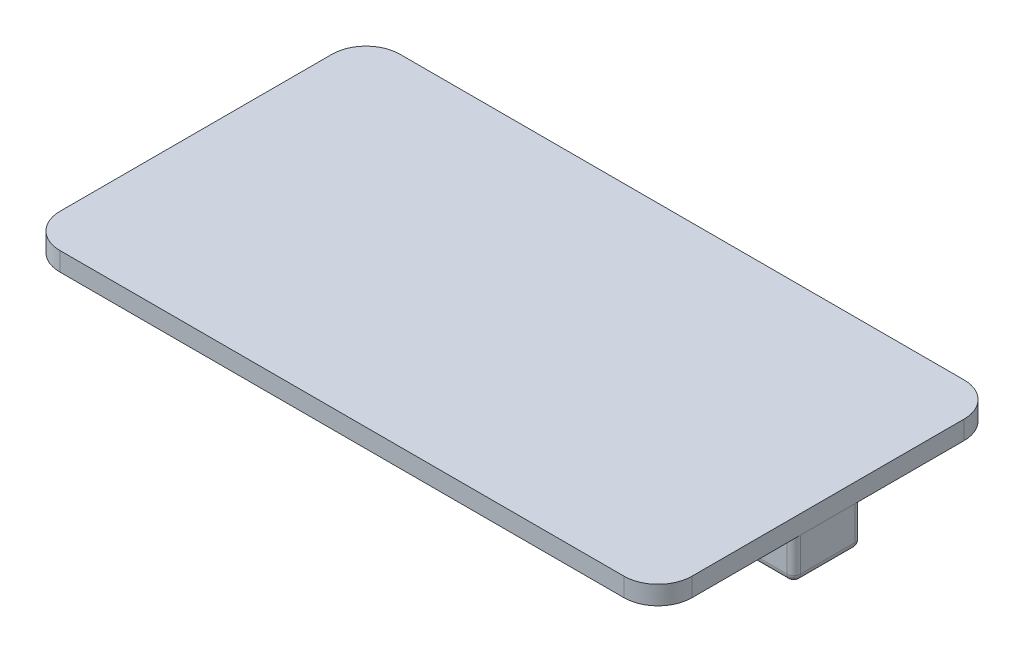
SolidWorks part; units mm, degrees
ref_plane "前视基准面" through (0, 0, 0) normal (0, 0, 1) x (1, 0, 0)
ref_plane "上视基准面" through (0, 0, 0) normal (0, 1, 0) x (1, 0, 0)
ref_plane "右视基准面" through (0, 0, 0) normal (1, 0, 0) x (0, 0, -1)
other "Configuration Table"
sketch "草图1" plane through (0, 0, 0) normal (0, 1, 0) x (1, 0, 0)
  line L1 (-93, 10) -> (93, 10)
  line L2 (-93, 10) -> (-93, -10)
  line L3 (-93, -10) -> (93, -10)
  line L4 (93, 10) -> (93, -10)
  line L5 (-93, 10) -> (93, -10) construction
  line L6 (-93, -10) -> (93, 10) construction
  point P0 (0, 0)
  dimension "D1" = 186
  dimension "D2" = 20
extrude "凸台-拉伸1" add sketch "草图1" along normal blind 14 contours L2 L1 L4 L3
sketch "草图2" plane through (0, 14, 0) normal (0, 1, 0) x (1, 0, 0)
  line L1 (-93, 10) -> (93, 10)
  line L2 (-93, 10) -> (-93, -10)
  line L3 (-93, -10) -> (93, -10)
  line L4 (93, 10) -> (93, -10)
  line L5 (-93, 10) -> (93, -10) construction
  line L6 (-93, -10) -> (93, 10) construction
  point P0 (0, 0)
  dimension "D1" = 186
  dimension "D2" = 20
extrude "切除-拉伸2" cut sketch "草图2" against normal blind 2
sketch "草图3" plane through (0, 0, 0) normal (0, -1, 0) x (1, 0, 0)
  line L1 (-88.5, 5.5) -> (88.5, 5.5)
  line L2 (-88.5, 5.5) -> (-88.5, -5.5)
  line L3 (-88.5, -5.5) -> (88.5, -5.5)
  line L4 (88.5, 5.5) -> (88.5, -5.5)
  line L5 (-88.5, 5.5) -> (88.5, -5.5) construction
  line L6 (-88.5, -5.5) -> (88.5, 5.5) construction
  point P0 (0, 0)
  dimension "D1" = 177
  dimension "D2" = 11
extrude "切除-拉伸3" cut sketch "草图3" against normal blind 4
sketch "草图4" plane through (0, 4, 0) normal (0, -1, 0) x (1, 0, 0)
  line L0 (0, 34.5012) -> (0, -30.2871) construction
  circle A0 centre (-72, 0) radius 2.75
  circle A1 centre (-38, 0) radius 2.75
  circle A2 centre (38, 0) radius 2.75
  circle A3 centre (72, 0) radius 2.75
  dimension "D5" = 5.5
  dimension "D6" = 5.5
  dimension "D7" = 5.5
  dimension "D8" = 5.5
  dimension "D1" = 38
  dimension "D2" = 72
  dimension "D3" = 38
  dimension "D4" = 72
extrude "切除-拉伸6" cut sketch "草图4" against normal blind 5.5
sketch "草图5" plane through (0, 12, 0) normal (0, 1, 0) x (1, 0, 0)
  line L0 (-92.7998, 50) -> (-92.7998, -50)
  line L1 (-92.7998, -50) -> (93.0804, -50)
  line L2 (93.0804, -50) -> (93.0804, 50)
  line L3 (93.0804, 50) -> (-92.7998, 50)
  line L4 (-115.6666, 0) -> (106.2674, 0) construction
  dimension "D1" = 50
  dimension "D2" = 50
extrude "凸台-拉伸2" add sketch "草图5" along normal blind 5.5
fillet "圆角1" radius 10 1 edges at (-92.7998, 14.75, 50)
fillet "圆角2" radius 10 1 edges at (93.0804, 14.75, 50)
fillet "圆角3" radius 10 1 edges at (93.0804, 14.75, -50)
fillet "圆角4" radius 10 1 edges at (-92.7998, 14.75, -50)
fillet "圆角6" radius 2 1 edges at (0, 0, -10)
fillet "圆角7" radius 2 1 edges at (0, 0, 10)
fillet "圆角8" radius 2 5 edges at (-93, 7, -10) (-93, 0.5858, -9.4142) (-93, 7, 10) (-93, 0.5858, 9.4142) (-93, 0, 0)
fillet "圆角9" radius 2 5 edges at (93, 7, -10) (93, 0.5858, -9.4142) (93, 7, 10) (93, 0.5858, 9.4142) (93, 0, 0)
